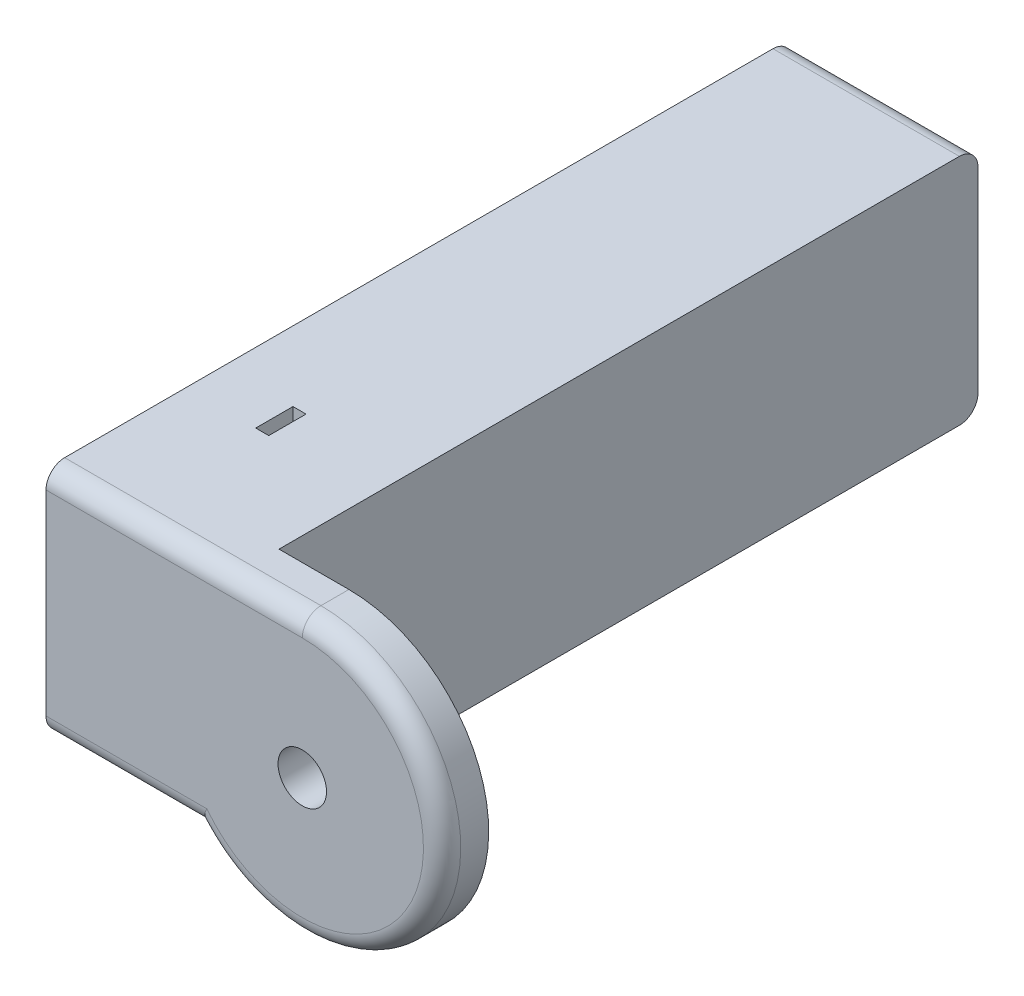
SolidWorks part; units mm, degrees
ref_plane "Front Plane" through (0, 0, 0) normal (0, 0, 1) x (1, 0, 0)
ref_plane "Top Plane" through (0, 0, 0) normal (0, 1, 0) x (1, 0, 0)
ref_plane "Right Plane" through (0, 0, 0) normal (1, 0, 0) x (0, 0, -1)
sketch "Sketch1" plane through (0, 0, 0) normal (0, 1, 0) x (1, 0, 0)
  line L0 (12.7, 50.8) -> (-12.7, -50.8) construction
  line L1 (-12.7, 50.8) -> (12.7, 50.8)
  line L2 (-12.7, 50.8) -> (-12.7, -50.8)
  line L3 (-12.7, -50.8) -> (12.7, -50.8)
  line L4 (12.7, 50.8) -> (12.7, -50.8)
  dimension "D1" = 25.4
  dimension "D2" = 101.6
extrude "Top" add sketch "Sketch1" along normal blind 4.7625
sketch "Sketch2" plane through (0, 4.7625, 0) normal (0, 1, 0) x (1, 0, 0)
  line L1 (-12.7, 50.8) -> (12.7, 50.8)
  line L2 (-12.7, 50.8) -> (-12.7, -50.8)
  line L3 (-12.7, -50.8) -> (12.7, -50.8)
  line L5 (12.7, 50.8) -> (12.7, -50.8)
  line L6 (-7.9375, 44.45) -> (7.9375, 44.45)
  line L7 (-7.9375, 44.45) -> (-7.9375, -44.45)
  line L8 (-7.9375, -44.45) -> (7.9375, -44.45)
  line L9 (7.9375, 44.45) -> (7.9375, -44.45)
  dimension "D1" = 4.7625
  dimension "D2" = 4.7625
  dimension "D3" = 6.35
  dimension "D4" = 6.35
extrude "Walls" add sketch "Sketch2" against normal blind 31.75
sketch "Sketch9" plane through (0, 0, 50.8) normal (0, 0, -1) x (-1, 0, 0)
  line L0 (-12.7, -14.2875) -> (-22.225, -14.2875) construction
  line L2 (12.7, -26.9875) -> (-12.7, -26.9875) construction
  line L3 (-22.225, 4.7625) -> (-12.7, 4.7625)
  line L7 (-12.7, 4.7625) -> (12.7, 4.7625) construction
  line L8 (-12.7, -26.9875) -> (-12.7, 4.7625)
  line L13 (-12.7, 4.7625) -> (-12.7, -26.9875) construction
  line L14 (-8.026, -26.9875) -> (-12.7, -26.9875)
  circle A0 centre (-22.225, -14.2875) radius 19.05 construction
  arc A1 (-22.225, 4.7625) -> (-8.026, -26.9875) centre (-22.225, -14.2875) ccw
  circle A2 centre (-22.225, -14.2875) radius 3.302
  dimension "D2" = 19.05
  dimension "D3" = 6.604
  dimension "D1" = 9.525
extrude "Joint Hinge" add sketch "Sketch9" along normal blind 6.35
sketch "Sketch3" plane through (-12.7, 0, 0) normal (-1, 0, 0) x (0, 0, 1)
  line L0 (-50.8, -11.1125) -> (-31.75, -11.1125) construction
  line L1 (-50.8, 4.7625) -> (-50.8, -26.9875) construction
  line L2 (50.8, -11.1125) -> (38.1, -11.1125) construction
  line L3 (50.8, 4.7625) -> (50.8, -26.9875) construction
  line L4 (-31.75, -11.1125) -> (-31.75, -26.9875) construction
  line L9 (-50.8, -26.9875) -> (50.8, -26.9875) construction
  line L11 (-25.6016, -12.7) -> (-23.0616, -12.7)
  line L13 (-25.6016, -9.525) -> (-23.0616, -9.525)
  line L14 (-23.0616, -12.7) -> (-23.0616, -9.525)
  line L15 (-25.6016, -12.7) -> (-23.0616, -9.525) construction
  line L16 (-25.6016, -9.525) -> (-23.0616, -12.7) construction
  circle A0 centre (38.1, -11.1125) radius 3.175
  circle A1 centre (-31.75, -11.1125) radius 6.35 construction
  arc A2 (-25.6016, -9.525) -> (-25.6016, -12.7) centre (-31.75, -11.1125) ccw
  point P13 (-24.3316, -11.1125)
  dimension "D3" = 6.35
  dimension "D4" = 12.7
  dimension "D1" = 19.05
  dimension "D2" = 12.7
  dimension "D5" = 15.875
  dimension "D6" = 3.175
  dimension "D7" = 2.54
extrude "Shaft holes" cut sketch "Sketch3" against normal blind 23.876
sketch "Sketch13" plane through (0, 0, 0) normal (0, -1, 0) x (1, 0, 0)
  line L1 (-3.175, 26.67) -> (-1.397, 26.67)
  line L2 (-3.175, 26.67) -> (-3.175, 31.75)
  line L3 (-3.175, 31.75) -> (-1.397, 31.75)
  line L4 (-1.397, 26.67) -> (-1.397, 31.75)
  line L5 (-12.7, 50.8) -> (12.7, 50.8) construction
  line L6 (-12.7, -50.8) -> (-12.7, 50.8) construction
  dimension "D1" = 1.778
  dimension "D2" = 5.08
  dimension "D3" = 19.05
  dimension "D4" = 9.525
extrude "Wire Loft Mount" cut sketch "Sketch13" against normal blind 12.7
fillet "Fillet1" radius 2.54 5 edges at (0, -26.9875, -50.8) (-2.337, -26.9875, 50.8) (39.6152, -22.0646, 50.8) (4.7625, 4.7625, 50.8) (0, 4.7625, -50.8)
